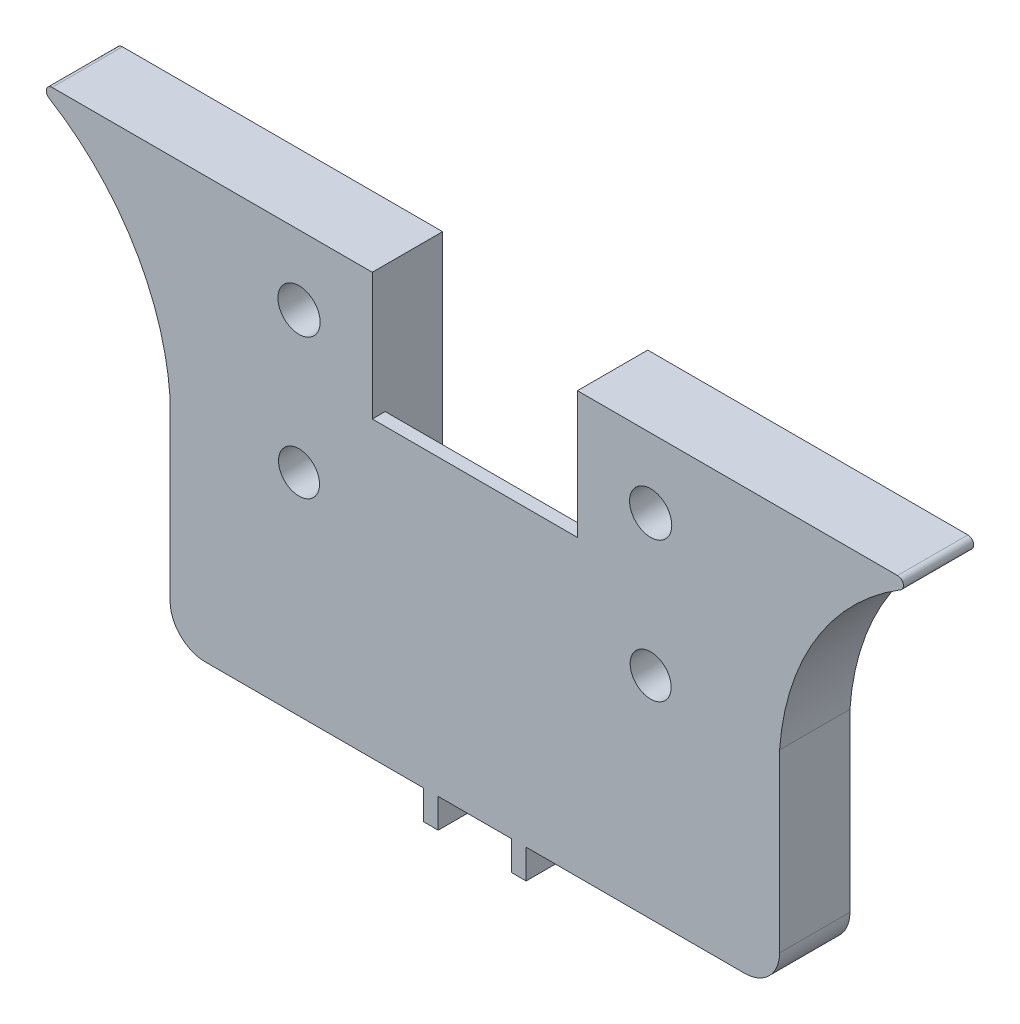
SolidWorks part; units mm, degrees
ref_plane "Front Plane" through (0, 0, 0) normal (0, 0, 1) x (1, 0, 0)
ref_plane "Top Plane" through (0, 0, 0) normal (0, 1, 0) x (1, 0, 0)
ref_plane "Right Plane" through (0, 0, 0) normal (1, 0, 0) x (0, 0, -1)
sketch "Sketch2" plane through (0, 0, 0) normal (0, 0, 1) x (1, 0, 0)
  line L0 (0, -33.2846) -> (0, 67.9981) construction
  line L12 (45.8007, 37.8996) -> (-45.8007, 37.8996)
  line L13 (-33.02, 15.1445) -> (-33.02, -3.9055)
  line L14 (-29.21, -7.7155) -> (29.21, -7.7155)
  line L15 (33.02, 15.1445) -> (33.02, -3.9055)
  circle A4 centre (-19.05, 15.1445) radius 2.2225
  circle A12 centre (19.05, 15.1445) radius 2.2225
  arc A13 (-33.02, 15.1445) -> (-46.1321, 36.723) centre (-60.5269, 13.203) ccw
  arc A14 (33.02, 15.1445) -> (46.1321, 36.723) centre (60.5269, 13.203) cw
  arc A15 (33.02, -3.9055) -> (29.21, -7.7155) centre (29.21, -3.9055) cw
  arc A16 (-33.02, -3.9055) -> (-29.21, -7.7155) centre (-29.21, -3.9055) ccw
  arc A17 (46.1321, 36.723) -> (45.8007, 37.8996) centre (45.8007, 37.2646) ccw
  arc A18 (-45.8007, 37.8996) -> (-46.1321, 36.723) centre (-45.8007, 37.2646) ccw
  point P4 (0, 57.6776)
  point P9 (0, 19.5776)
  point P12 (0, 37.8996)
  point P16 (0, -7.7155)
  point P18 (33.02, -7.7155)
  point P20 (0, -3.9055)
  point P22 (-33.02, -7.7155)
  point P27 (48.26, 37.8996)
  point P30 (-48.26, 37.8996)
  dimension "D2" = 48.26
  dimension "D3" = 22.86
  dimension "D6" = 0.635
  dimension "D4" = 33.02
  dimension "D5" = 3.81
  dimension "D7" = 27.5753
  dimension "D8" = 19.05
  dimension "D9" = 45.8007
  dimension "D10" = 19.05
  dimension "D11" = 19.5776
  dimension "D12" = 57.6776
  dimension "D1" = 4.445
extrude "Boss-Extrude1" add sketch "Sketch2" along normal blind 7.62
sketch "Sketch11" plane through (0, 0, 7.62) normal (0, 0, 1) x (1, 0, 0)
  line L0 (0, 41.9648) -> (0, -47.1588) construction
  line L1 (-19.05, 15.1445) -> (-19.05, 30.3845) construction
  circle A0 centre (-19.05, 30.3845) radius 2.286
  circle A1 centre (19.05, 30.3845) radius 2.286
  dimension "D2" = 4.572
  dimension "D1" = 15.24
extrude "Cut-Extrude9" cut sketch "Sketch11" against normal through all
sketch "Sketch12" plane through (0, 0, 0) normal (0, 0, 1) x (1, 0, 0)
  line L0 (0, 39.594) -> (0, -43.4023) construction
  line L1 (-4.7625, 33.4498) -> (4.7625, 33.4498)
  line L3 (4.7625, 10.9708) -> (-4.7625, 10.9708)
  line L4 (-11.1125, 17.3208) -> (-11.1125, 27.0998)
  line L5 (11.1125, 17.3208) -> (11.1125, 27.0998)
  arc A0 (11.1125, 27.0998) -> (4.7625, 33.4498) centre (4.7625, 27.0998) ccw
  arc A1 (11.1125, 17.3208) -> (4.7625, 10.9708) centre (4.7625, 17.3208) cw
  arc A2 (-4.7625, 10.9708) -> (-11.1125, 17.3208) centre (-4.7625, 17.3208) cw
  arc A3 (-4.7625, 33.4498) -> (-11.1125, 27.0998) centre (-4.7625, 27.0998) ccw
  point P10 (0, 10.9708)
  point P11 (0, 33.4498)
  point P13 (11.1125, 33.4498)
  point P16 (11.1125, 10.9708)
  point P19 (-11.1125, 10.9708)
  point P22 (-11.1125, 33.4498)
  dimension "D4" = 6.35
  dimension "D1" = 11.1125
  dimension "D2" = 10.9708
  dimension "D3" = 22.479
extrude "Cut-Extrude11" cut sketch "Sketch12" along normal blind 6.223
sketch "Sketch13" plane through (0, 0, 0) normal (0, 0, -1) x (-1, 0, 0)
  line L2 (-11.1125, 40.3062) -> (-11.1125, 24.1288)
  line L3 (-11.1125, 24.1288) -> (11.1125, 24.1288)
  line L7 (-11.1125, 40.3062) -> (11.1125, 40.3062)
  line L8 (11.1125, 40.3062) -> (11.1125, 24.1288)
  dimension "D1" = 11.1125
  dimension "D2" = 11.1125
  dimension "D3" = 24.1288
  dimension "D4" = 40.3062
extrude "Cut-Extrude12" cut sketch "Sketch13" against normal through all
sketch "Sketch15" plane through (0, -7.7155, 0) normal (0, -1, 0) x (1, 0, 0)
  line L0 (0, -11.1019) -> (0, 17.7532) construction
  line L1 (-29.21, 3.81) -> (29.21, 3.81) construction
  line L4 (-29.21, 7.62) -> (-29.21, 0) construction
  line L5 (29.21, 7.62) -> (29.21, 0) construction
  circle A0 centre (0, 3.81) radius 2.032
  dimension "D1" = 4.064
extrude "Cut-Extrude14" cut sketch "Sketch15" against normal blind 17.78
sketch "Sketch16" plane through (0, 0, 0) normal (0, 0, -1) x (-1, 0, 0)
  line L0 (29.21, -7.7155) -> (-29.21, -7.7155) construction
  line L1 (-3.9687, -7.7155) -> (-5.5563, -7.7155)
  line L2 (-3.9687, -7.7155) -> (-3.9688, -10.8905)
  line L3 (-3.9688, -10.8905) -> (-5.5563, -10.8905)
  line L4 (-5.5563, -7.7155) -> (-5.5563, -10.8905)
  line L5 (0, -11.3212) -> (0, 10.1435) construction
  line L6 (5.5562, -7.7155) -> (3.9688, -7.7155)
  line L7 (5.5562, -7.7155) -> (5.5562, -10.8905)
  line L8 (5.5562, -10.8905) -> (3.9688, -10.8905)
  line L9 (3.9688, -7.7155) -> (3.9688, -10.8905)
  dimension "D1" = 1.5875
  dimension "D2" = 3.175
  dimension "D3" = 7.9375
  dimension "D4" = 3.9688
extrude "Boss-Extrude2" add sketch "Sketch16" against normal up to surface (7.62 mm away) up to face at (-16.764, 30.3845, 7.62)
equation "\"D4@Sketch16\"=\"D3@Sketch16\"/2"
